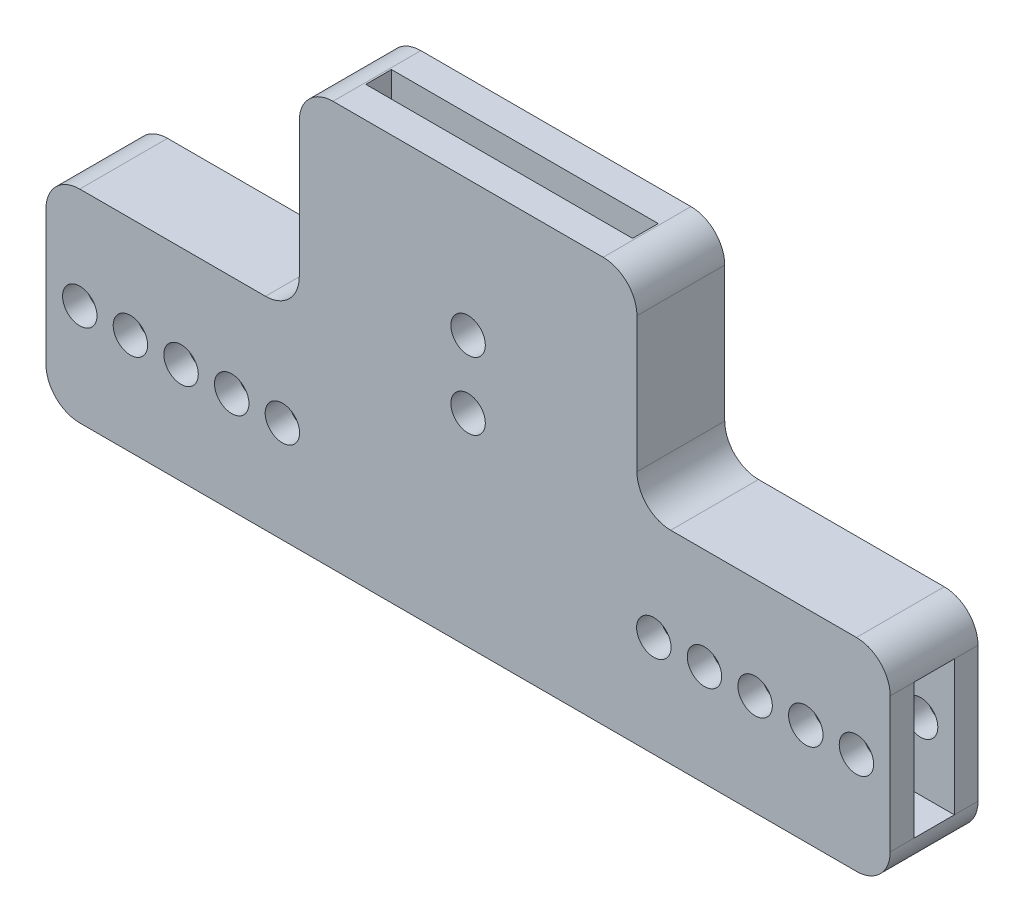
SolidWorks part; units mm, degrees
ref_plane "Front Plane" through (0, 0, 0) normal (0, 0, 1) x (1, 0, 0)
ref_plane "Top Plane" through (0, 0, 0) normal (0, 1, 0) x (1, 0, 0)
ref_plane "Right Plane" through (0, 0, 0) normal (1, 0, 0) x (0, 0, -1)
sketch "Sketch1" plane through (0, 0, 0) normal (0, 0, 1) x (1, 0, 0)
  line L1 (-25, 30) -> (25, 30)
  line L2 (-25, 30) -> (-25, -30)
  line L3 (-25, -30) -> (25, -30)
  line L4 (25, 30) -> (25, -30)
  line L5 (-25, 30) -> (25, -30) construction
  line L6 (-25, -30) -> (25, 30) construction
  point P0 (0, 0)
extrude "Boss-Extrude1" add sketch "Sketch1" along normal blind 13
sketch "Sketch2" plane through (0, 30, 0) normal (0, 1, 0) x (1, 0, 0)
  line L1 (-19.75, -4.6) -> (19.75, -4.6)
  line L2 (-19.75, -4.6) -> (-19.75, -8.4)
  line L3 (-19.75, -8.4) -> (19.75, -8.4)
  line L4 (19.75, -4.6) -> (19.75, -8.4)
  line L5 (-19.75, -4.6) -> (19.75, -8.4) construction
  line L6 (-19.75, -8.4) -> (19.75, -4.6) construction
  line L8 (-25, -6.5) -> (25, -6.5) construction
  line L9 (-25, -13) -> (-25, 0) construction
  line L10 (25, -13) -> (25, 0) construction
  point P0 (0, -6.5)
  dimension "D1" = 1.9
  dimension "D2" = 3.8
  dimension "D3" = 5.25
  dimension "D4" = 5.25
extrude "Cut-Extrude1" cut sketch "Sketch2" against normal through all
sketch "Sketch3" plane through (-25, 0, 0) normal (-1, 0, 0) x (0, 0, 1)
  line L0 (13, 30) -> (13, -30) construction
  line L1 (0, -30) -> (13, -30)
  line L2 (0, -30) -> (0, 0)
  line L3 (0, 0) -> (13, 0)
  line L4 (13, -30) -> (13, 0)
  line L5 (6.5, 0) -> (6.5, -30) construction
  line L6 (0, -15) -> (13, -15) construction
  point P1024 (6.5, -15)
  dimension "D1" = 30
extrude "Boss-Extrude2" add sketch "Sketch3" along normal blind 37.5
sketch "Sketch4" plane through (-62.5, 0, 0) normal (-1, 0, 0) x (0, 0, 1)
  line L0 (13, 0) -> (0, 0) construction
  line L1 (3.5, -5) -> (9.5, -5)
  line L2 (3.5, -5) -> (3.5, -25)
  line L3 (3.5, -25) -> (9.5, -25)
  line L4 (9.5, -5) -> (9.5, -25)
  line L5 (3.5, -5) -> (9.5, -25) construction
  line L6 (3.5, -25) -> (9.5, -5) construction
  line L9 (0, -30) -> (13, -30) construction
  line L10 (6.5, 0) -> (6.5, -30) construction
  point P0 (6.5, -15)
  dimension "D1" = 5
  dimension "D2" = 3
  dimension "D3" = 3
  dimension "D4" = 5
extrude "Cut-Extrude2" cut sketch "Sketch4" against normal blind 40
sketch "Sketch5" plane through (0, 0, 13) normal (0, 0, 1) x (1, 0, 0)
  line L0 (-62.5, -5) -> (-62.5, -25) construction
  circle A0 centre (-57.5, -14.9958) radius 2.55
  circle A1 centre (-50, -14.9958) radius 2.55
  circle A2 centre (-42.5, -14.9958) radius 2.55
  circle A3 centre (-35, -14.9958) radius 2.55
  circle A4 centre (-27.5, -14.9958) radius 2.55
  dimension "D1" = 5
  dimension "D2" = 5
extrude "Cut-Extrude3" cut sketch "Sketch5" against normal blind 35
mirror "Mirror1" about plane through (0, 0, 0) normal (1, 0, 0) of "Cut-Extrude3", "Cut-Extrude2", "Boss-Extrude2"
fillet "Fillet1" radius 5 8 edges at (62.5, -30, 6.5) (62.5, 0, 6.5) (25, 0, 6.5) (-62.5, -30, 6.5) (-62.5, 0, 6.5) (-25, 0, 6.5) (25, 30, 6.5) (-25, 30, 6.5)
sketch "Sketch6" plane through (0, 0, 13) normal (0, 0, 1) x (1, 0, 0)
  circle A0 centre (0, 0) radius 2.55
  circle A1 centre (0, 10) radius 2.55
  dimension "D1" = 10
extrude "Cut-Extrude4" cut sketch "Sketch6" against normal blind 35
